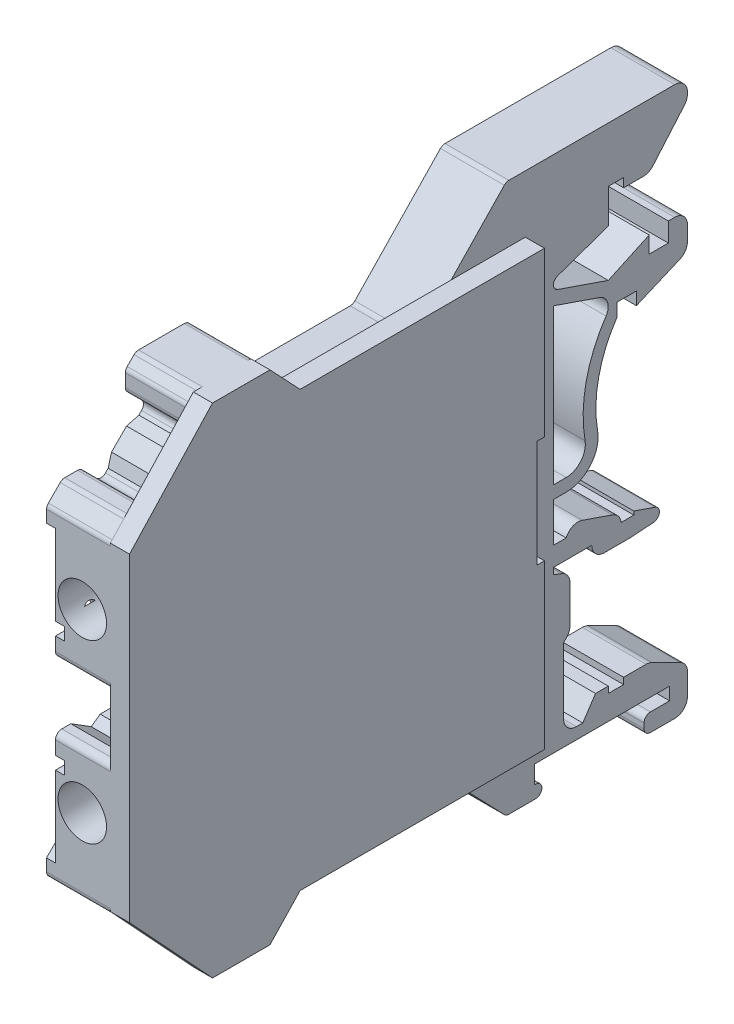
SolidWorks part; units mm, degrees
material "Polyethylene Cross-Linked"
ref_plane "Front Plane" through (0, 0, 0) normal (0, 0, 1) x (1, 0, 0)
ref_plane "Top Plane" through (0, 0, 0) normal (0, 1, 0) x (1, 0, 0)
ref_plane "Right Plane" through (0, 0, 0) normal (1, 0, 0) x (0, 0, -1)
sketch "Sketch2" plane through (0, 0, 0) normal (1, 0, 0) x (0, 0, -1)
  line L1 (-22.6, 21.5) -> (22.6, 21.5)
  line L2 (-22.6, 21.5) -> (-22.6, -21.5)
  line L3 (-22.6, -21.5) -> (22.6, -21.5)
  line L4 (22.6, 21.5) -> (22.6, -21.5)
  line L5 (-22.6, 21.5) -> (22.6, -21.5) construction
  line L6 (-22.6, -21.5) -> (22.6, 21.5) construction
  point P0 (0, 0)
  dimension "D1" = 45.2
  dimension "D2" = 43
extrude "Boss-Extrude1" add sketch "Sketch2" along normal mid plane 5
sketch "Sketch3" plane through (0, 0, 0) normal (1, 0, 0) x (0, 0, -1)
  line L0 (-22.6, 12.5) -> (-22.6, -12.5)
  line L1 (-22.6, 21.5) -> (-22.6, -21.5) construction
  line L2 (-22.6, 12.5) -> (-15.6, 19.5)
  line L3 (-15.6, 19.5) -> (-11.6, 19.5)
  line L4 (-11.6, 19.5) -> (-6.6, 14.2)
  line L5 (-6.6, 14.2) -> (1.4, 14.2)
  line L6 (1.4, 14.2) -> (8.4, 21.5)
  line L7 (-22.6, -12.5) -> (-15.6, -19.5)
  line L8 (-15.6, -19.5) -> (-11.6, -19.5)
  line L9 (8.4, 21.5) -> (15.9349, 21.5)
  line L10 (15.9349, 21.5) -> (15.9349, 44.6195)
  line L11 (15.9349, 44.6195) -> (-57.4702, 44.6195)
  line L12 (-57.4702, 44.6195) -> (-57.4702, -44.6195)
  line L13 (-57.4702, -44.6195) -> (15.9349, -44.6195)
  line L14 (15.9349, -44.6195) -> (15.9349, -21.5)
  line L15 (15.9349, -21.5) -> (8.4, -21.5)
  line L16 (8.4, -21.5) -> (1.4, -14.2)
  line L17 (1.4, -14.2) -> (-6.6, -14.2)
  line L18 (-6.6, -14.2) -> (-11.6, -19.5)
  point P5 (-22.6, 0)
  dimension "D1" = 25
  dimension "D2" = 39
  dimension "D3" = 7
  dimension "D4" = 4
  dimension "D5" = 28.4
  dimension "D6" = 16
  dimension "D7" = 8
  dimension "D8" = 43
  dimension "D9" = 31
  dimension "D10" = 7.5349
  dimension "D11" = 73.4051
  dimension "D12" = 89.239
extrude "Cut-Extrude1" cut sketch "Sketch3" against normal mid plane 25
sketch "Sketch4" plane through (2.5, 0, 0) normal (1, 0, 0) x (0, 0, -1)
  line L0 (-19.7747, 20.6036) -> (-14.8021, 15.631)
  line L1 (-19.7747, 20.6036) -> (-23.3102, 17.0681)
  line L2 (-14.8021, 15.631) -> (-18.3376, 12.0955)
  line L3 (-23.3102, 17.0681) -> (-18.3376, 12.0955)
  line L4 (-19.7747, 20.6036) -> (-18.3376, 12.0955) construction
  line L5 (-14.8021, 15.631) -> (-23.3102, 17.0681) construction
  line L6 (-22.6, 12.5) -> (-15.6, 19.5) construction
  line L8 (0, 0) -> (-48.1398, 0) construction
  line L9 (-14.8021, -15.631) -> (-23.3102, -17.0681) construction
  line L10 (-19.7747, -20.6036) -> (-18.3376, -12.0955) construction
  line L11 (-23.3102, -17.0681) -> (-18.3376, -12.0955)
  line L12 (-14.8021, -15.631) -> (-18.3376, -12.0955)
  line L13 (-19.7747, -20.6036) -> (-23.3102, -17.0681)
  line L14 (-19.7747, -20.6036) -> (-14.8021, -15.631)
  point P1 (-19.0561, 16.3495)
  point P15 (-19.0561, -16.3495)
  dimension "D1" = 5
  dimension "D2" = 3.3
  dimension "D3" = 5
  dimension "D4" = 4.9726
extrude "Cut-Extrude2" cut sketch "Sketch4" against normal mid plane 25
sketch "Sketch6" plane through (0, 0, 0) normal (1, 0, 0) x (0, 0, -1)
  line L0 (-22.6, 12.5) -> (-22.6, -12.5) construction
  line L1 (-31.6, 2.5) -> (-13.6, 2.5)
  line L2 (-31.6, 2.5) -> (-31.6, -2.5)
  line L3 (-31.6, -2.5) -> (-13.6, -2.5)
  line L4 (-13.6, 2.5) -> (-13.6, -2.5)
  line L5 (-31.6, 2.5) -> (-13.6, -2.5) construction
  line L6 (-31.6, -2.5) -> (-13.6, 2.5) construction
  point P0 (-22.6, 0)
  dimension "D1" = 5
  dimension "D2" = 18
extrude "Cut-Extrude3" cut sketch "Sketch6" against normal through all both and the other way through all
chamfer "Chamfer1" distance 1 angle 45 4 edges at (0, -17.9645, 17.1355) (0, -14.4289, 20.6711) (0, 14.4289, 20.6711) (0, 17.9645, 17.1355)
sketch "Sketch8" plane through (0, 0, 22.6) normal (0, 0, 1) x (1, 0, 0)
  line L0 (0.3, 6.9) -> (0.3, -6.9) construction
  line L1 (2.2, 6.9) -> (2.5, 6.9) construction
  line L2 (2.5, 12.5) -> (2.5, 2.5) construction
  line L3 (0, 0) -> (0.3, 0) construction
  circle A0 centre (0.3, 6.9) radius 1.9
  circle A1 centre (0.3, -6.9) radius 1.9
  point P4 (0, 0)
  dimension "D1" = 3.8
  dimension "D2" = 13.8
  dimension "D3" = 0.3
extrude "Cut-Extrude4" cut sketch "Sketch8" against normal blind 25
sketch "Sketch9" plane through (2.5, 0, 0) normal (1, 0, 0) x (0, 0, -1)
  line L0 (-15.7213, 15.4189) -> (-18.1255, 13.0147)
  line L1 (-15.7213, 15.4189) -> (-15.0142, 14.7118)
  line L2 (-18.1255, 13.0147) -> (-17.4184, 12.3076)
  line L3 (-15.0142, 14.7118) -> (-17.4184, 12.3076)
  line L4 (-15.7213, 15.4189) -> (-17.4184, 12.3076) construction
  line L5 (-18.1255, 13.0147) -> (-15.0142, 14.7118) construction
  line L6 (-18.3376, 12.0955) -> (-14.8021, 15.631) construction
  line L7 (0, 0) -> (-33.3494, 0) construction
  line L8 (-18.1255, -13.0147) -> (-15.0142, -14.7118) construction
  line L9 (-15.7213, -15.4189) -> (-17.4184, -12.3076) construction
  line L10 (-15.0142, -14.7118) -> (-17.4184, -12.3076)
  line L11 (-18.1255, -13.0147) -> (-17.4184, -12.3076)
  line L12 (-15.7213, -15.4189) -> (-15.0142, -14.7118)
  line L13 (-15.7213, -15.4189) -> (-18.1255, -13.0147)
  point P1 (-16.5698, 13.8632)
  point P14 (-16.5698, -13.8632)
  dimension "D1" = 0.5
  dimension "D2" = 3.4
extrude "Boss-Extrude2" add sketch "Sketch9" against normal up to surface (5 mm away) up to face at (-2.5, 0, 11.1692)
chamfer "Chamfer2" distance 0.5 angle 60 2 edges at (0, -13.0147, 18.1255) (0, 15.4189, 15.7213)
chamfer "Chamfer3" distance 0.5 angle 60 2 edges at (0, 13.0147, 18.1255) (0, -15.4189, 15.7213)
sketch "Sketch10" plane through (-2.5, 0, 0) normal (-1, 0, 0) x (0, 0, 1)
  line L0 (19.1, 3) -> (13.6, 3)
  line L1 (19.1, 3) -> (19.1, -3)
  line L2 (13.6, 3) -> (13.6, -3)
  line L3 (19.1, -3) -> (13.6, -3)
  line L4 (19.1, 3) -> (13.6, -3) construction
  line L5 (13.6, 3) -> (19.1, -3) construction
  line L6 (13.6, -2.5) -> (13.6, 2.5) construction
  point P0 (13.6, 0)
  point P1 (16.35, 0)
  dimension "D1" = 6
  dimension "D2" = 5.5
extrude "Cut-Extrude5" cut sketch "Sketch10" against normal blind 25
sketch "Sketch11" plane through (2.5, 0, 0) normal (1, 0, 0) x (0, 0, -1)
  line L2 (-19.8, 3.5) -> (-19.8, -3.5) construction
  line L3 (-22.6, 12.5) -> (-22.6, 2.5) construction
  line L4 (-19.1, -3) -> (-19.8, -3.5)
  line L5 (-19.8, -3.5) -> (-21.4, -2.5)
  line L6 (-22.6, -2.5) -> (-19.1, -2.5) construction
  line L7 (-21.4, -2.5) -> (-21.4, 2.5)
  line L8 (-21.4, 2.5) -> (-19.8, 3.5)
  line L9 (-19.8, 3.5) -> (-19.1, 3)
  line L10 (-19.1, 3) -> (-19.1, -3)
  line L11 (-19.1, 2.5) -> (-22.6, 2.5) construction
  circle A0 centre (-19.8, 2.9) radius 0.6 construction
  circle A1 centre (-19.8, -2.9) radius 0.6 construction
  point P6 (-19.8, 0)
  dimension "D1" = 1.2
  dimension "D4" = 1.2
  dimension "D2" = 7
  dimension "D3" = 2.8
extrude "Cut-Extrude6" cut sketch "Sketch11" against normal blind 10
sketch "Sketch12" plane through (-2.5, 0, 0) normal (-1, 0, 0) x (0, 0, 1)
  line L0 (22.6, 12.5) -> (22.6, 2.5) construction
  line L1 (33.6, 9.35) -> (11.6, 9.35)
  line L2 (33.6, 9.35) -> (33.6, -9.35)
  line L3 (33.6, -9.35) -> (11.6, -9.35)
  line L4 (11.6, 9.35) -> (11.6, -9.35)
  line L5 (33.6, 9.35) -> (11.6, -9.35) construction
  line L6 (33.6, -9.35) -> (11.6, 9.35) construction
  point P0 (22.6, 0)
  dimension "D1" = 18.7
  dimension "D2" = 11
extrude "Cut-Extrude7" cut sketch "Sketch12" against normal blind 0.7
sketch "Sketch13" plane through (-2.5, 0, 0) normal (-1, 0, 0) x (0, 0, 1)
  line L0 (22.6, 9.35) -> (22.6, 2.5) construction
  line L1 (32.2, 4.75) -> (13, 4.75)
  line L2 (32.2, 4.75) -> (32.2, 4.05)
  line L3 (32.2, 4.05) -> (13, 4.05)
  line L4 (13, 4.75) -> (13, 4.05)
  line L5 (32.2, 4.75) -> (13, 4.05) construction
  line L6 (32.2, 4.05) -> (13, 4.75) construction
  line L7 (22.6, -2.5) -> (22.6, -9.35) construction
  line L8 (32.2, -4.05) -> (13, -4.05)
  line L9 (32.2, -4.05) -> (32.2, -4.75)
  line L10 (32.2, -4.75) -> (13, -4.75)
  line L11 (13, -4.05) -> (13, -4.75)
  line L12 (32.2, -4.05) -> (13, -4.75) construction
  line L13 (32.2, -4.75) -> (13, -4.05) construction
  line L14 (0, 0) -> (27.7883, 0) construction
  line L15 (20.6, 5.75) -> (20.6, -5.75) construction
  line L16 (32.2, 4.75) -> (16.9, 4.75)
  line L17 (32.2, 4.75) -> (32.2, 5.05)
  line L18 (32.2, 5.05) -> (16.9, 5.05)
  line L19 (16.9, 4.75) -> (16.9, 5.05)
  line L20 (32.2, -4.75) -> (16.9, -4.75)
  line L21 (32.2, -4.75) -> (32.2, -5.05)
  line L22 (32.2, -5.05) -> (16.9, -5.05)
  line L23 (16.9, -4.75) -> (16.9, -5.05)
  circle A0 centre (20.6, 5.05) radius 0.7
  circle A1 centre (20.6, -5.05) radius 0.7
  point P0 (22.6, 4.4)
  point P7 (22.6, -4.4)
  dimension "D7" = 2
  dimension "D1" = 9.5
  dimension "D2" = 0.7
  dimension "D3" = 9.6
  dimension "D4" = 1
  dimension "D5" = 5.7
  dimension "D6" = 11.5
extrude "Cut-Extrude9" cut sketch "Sketch13" against normal blind 1.4 contours L2 L3 L4 L1 | L17 L18 L19 L16 | A0 | L9 L8 L11 L10 | L21 L22 L23 L20 | A1
sketch "Sketch14" plane through (0, 0, 0) normal (1, 0, 0) x (0, 0, -1)
  line L2 (-22.6, 21.5) -> (-22.6, -21.5) construction
  line L3 (16.4, 17.2) -> (17.6, 17.2)
  line L4 (16.4, 17.2) -> (16.4, -17.2)
  line L5 (16.4, -17.2) -> (17.6, -17.2)
  line L6 (17.6, 17.2) -> (17.6, -17.2)
  line L7 (16.4, 17.2) -> (17.6, -17.2) construction
  line L8 (16.4, -17.2) -> (17.6, 17.2) construction
  point P4 (17, 0)
  dimension "D1" = 34.4
  dimension "D2" = 1.2
  dimension "D3" = 39
extrude "Cut-Extrude10" cut sketch "Sketch14" against normal through all both and the other way through all
sketch "Sketch15" plane through (2.5, 0, 0) normal (1, 0, 0) x (0, 0, -1)
  line L0 (22.6, 21.5) -> (22.6, 20) construction
  line L1 (22.6, -21.5) -> (22.6, 21.5) construction
  line L2 (22.6, 20) -> (19.6, 16.5)
  line L3 (19.6, 16.5) -> (17.6, 16.5)
  line L4 (17.6, -17.2) -> (17.6, 17.2) construction
  line L5 (22.6, 21.5) -> (8.4, 21.5) construction
  line L6 (16.4, 14.5) -> (12.1, 13)
  line L7 (16.4, 17.2) -> (16.4, -17.2) construction
  line L8 (12.1, 13) -> (12.1, -7)
  line L9 (12.1, -7) -> (13.4, -7.5)
  line L10 (13.4, -7.5) -> (13.4, -11.5)
  line L11 (13.4, -11.5) -> (12.9, -12)
  line L12 (12.9, -12) -> (12.9, -16.7)
  line L13 (12.9, -16.7) -> (58.7234, -16.7)
  line L14 (-22.6, 12.5) -> (-22.6, 2.5) construction
  line L15 (22.6, 21.5) -> (8.4, 21.5) construction
  line L16 (-22.6, -2.5) -> (-22.6, -12.5) construction
  line L17 (17.6, 16.5) -> (16.4, 16.5)
  line L18 (16.4, 16.5) -> (16.4, 14.5)
  line L19 (22.6, 20) -> (58.7234, 20)
  line L20 (58.7234, 20) -> (58.7234, -16.7)
  dimension "D1" = 5
  dimension "D2" = 1.5
  dimension "D3" = 2
  dimension "D4" = 34.7
  dimension "D5" = 8.5
  dimension "D6" = 7
  dimension "D7" = 20
  dimension "D8" = 5
  dimension "D9" = 4.7
  dimension "D10" = 36
  dimension "D11" = 0.5
  dimension "D12" = 0.5
  dimension "D13" = 4
  dimension "D14" = 35.5
  dimension "D15" = 36.1234
extrude "Cut-Extrude11" cut sketch "Sketch15" against normal blind 7
sketch "Sketch16" plane through (2.5, 0, 0) normal (1, 0, 0) x (0, 0, -1)
  line L0 (12.1, 12.3) -> (16.4, 10.8194)
  line L1 (12.1, 13) -> (12.1, -7) construction
  line L2 (16.4, 10.8194) -> (19.6, 12.3)
  line L3 (19.6, 12.3) -> (19.6, 11)
  line L4 (19.6, 11) -> (21.1, 11)
  line L5 (21.1, 11) -> (21.1, 12.5)
  line L6 (21.1, 12.5) -> (22.6, 12.5)
  line L7 (22.6, 12.5) -> (22.6, 9.7)
  line L8 (22.6, 9.7) -> (18.6, 8)
  line L9 (18.6, 8) -> (18.6, 9)
  line L10 (18.6, 9) -> (17.1, 9)
  line L11 (17.1, 9) -> (17.1, 8)
  line L12 (22.6, 21.5) -> (22.6, -21.5) construction
  line L13 (-22.6, 21.5) -> (22.6, 21.5) construction
  line L14 (12.1, -1.9) -> (14.7278, -1.9) construction
  line L15 (13.1, -1.9) -> (12.1, -1.9)
  line L16 (12.1, -1.9) -> (12.1, 12.3)
  arc A0 (17.1, 8) -> (15.5644, 1.0206) centre (24.929, 2.6188) ccw
  arc A1 (15.5644, 1.0206) -> (13.1, -1.9) centre (13.1, 0.6) cw
  dimension "D13" = 2.5
  dimension "D15" = 9.5
  dimension "D1" = 109
  dimension "D2" = 0.7
  dimension "D3" = 1.5
  dimension "D4" = 1.5
  dimension "D5" = 9
  dimension "D6" = 1.5
  dimension "D7" = 4.5
  dimension "D8" = 2.8
  dimension "D9" = 4
  dimension "D10" = 1.5
  dimension "D11" = 1
  dimension "D12" = 23.4
  dimension "D14" = 1
extrude "Boss-Extrude3" add sketch "Sketch16" against normal up to surface (5 mm away) up to face at (-2.5, -0.4418, 3.4082)
sketch "Sketch17" plane through (2.5, 0, 0) normal (1, 0, 0) x (0, 0, -1)
  line L2 (12.1, -0.9) -> (13.1, -0.9)
  line L3 (12.1, -0.9) -> (13.1, -0.9)
  line L4 (12.1, 12.3) -> (12.1, -1.9) construction
  line L5 (16.0744, 9.8739) -> (11.7744, 11.3545)
  line L6 (15.721, 9.9956) -> (12.1, 11.2424)
  line L7 (12.1, 11.2424) -> (12.1, -0.9)
  arc A5 (16.2244, 8.4908) -> (15.721, 9.9956) centre (15.3954, 9.0501) ccw
  arc A7 (16.2759, 8.5664) -> (14.5786, 0.8524) centre (24.929, 2.6188) ccw
  arc A8 (13.1, -0.9) -> (14.5786, 0.8524) centre (13.1, 0.6) ccw
  arc A9 (16.2244, 8.4908) -> (14.5786, 0.8524) centre (24.929, 2.6188) ccw
  arc A10 (13.1, -0.9) -> (14.5786, 0.8524) centre (13.1, 0.6) ccw
  dimension "D3" = 1
  dimension "D1" = 1
  dimension "D2" = 1
extrude "Cut-Extrude12" cut sketch "Sketch17" against normal blind 7
sketch "Sketch18" plane through (2.5, 0, 0) normal (1, 0, 0) x (0, 0, -1)
  line L0 (12.1, -5) -> (13.1, -5)
  line L1 (12.1, -1.9) -> (12.1, -7) construction
  line L2 (13.1, -5) -> (13.1, -4)
  line L3 (13.1, -4) -> (17.4, -5.4806)
  line L4 (17.4, -5.4806) -> (17.4, -6.1)
  line L5 (17.4, -6.1) -> (18.4, -6.1)
  line L6 (18.4, -6.1) -> (18.4, -5.8249)
  line L7 (18.4, -5.8249) -> (20.067, -6.3989)
  line L8 (19.9394, -7.3705) -> (18.1, -7.5)
  line L9 (18.1, -7.5) -> (15.1, -7.5)
  line L10 (15.1, -7.5) -> (15.1, -6.5)
  line L11 (15.1, -6.5) -> (12.1, -6.5)
  line L12 (12.1, -6.5) -> (12.1, -5)
  line L13 (16.4, 10.8194) -> (12.1, 12.3) construction
  line L14 (-22.6, -2.5) -> (-22.6, -12.5) construction
  line L15 (20.4, -6.9368) -> (20.4, -8.2286) construction
  line L16 (-22.6, 21.5) -> (22.6, 21.5) construction
  line L17 (-22.6, 21.5) -> (-22.6, -21.5) construction
  arc A0 (20.067, -6.3989) -> (19.9394, -7.3705) centre (19.9043, -6.8717) cw
  dimension "D10" = 0.5
  dimension "D1" = 1.5
  dimension "D2" = 3.5
  dimension "D3" = 1.4
  dimension "D4" = 1
  dimension "D5" = 1
  dimension "D6" = 1
  dimension "D7" = 40
  dimension "D8" = 3
  dimension "D9" = 3
  dimension "D11" = 29
  dimension "D12" = 43
extrude "Boss-Extrude4" add sketch "Sketch18" against normal up to surface (5 mm away) up to face at (-2.5, 4.7868, -13.9775)
sketch "Sketch20" plane through (2.5, 0, 0) normal (1, 0, 0) x (0, 0, -1)
  line L0 (12.9, -16.7) -> (12.9, -18.2)
  line L1 (12.9, -18.2) -> (14.4, -18.2)
  line L2 (14.4, -18.2) -> (15.4, -16.7)
  line L3 (12.9, -16.7) -> (16.4, -16.7) construction
  line L4 (15.4, -16.7) -> (12.9, -16.7)
  line L5 (19.6, -16.7) -> (22.6, -18.2)
  line L6 (17.6, -16.7) -> (22.6, -16.7) construction
  line L7 (22.6, 21.5) -> (22.6, -21.5) construction
  line L8 (22.6, -18.2) -> (22.6, -16.7)
  line L9 (22.6, -16.7) -> (19.6, -16.7)
  line L10 (-22.6, -21.5) -> (22.6, -21.5) construction
  line L11 (21.2, -20.1) -> (11.2, -20.1)
  line L12 (21.2, -20.1) -> (21.2, -19.1)
  line L13 (21.2, -19.1) -> (11.2, -19.1)
  line L14 (11.2, -20.1) -> (11.2, -19.1)
  line L15 (21.2, -20.1) -> (11.2, -19.1) construction
  line L16 (21.2, -19.1) -> (11.2, -20.1) construction
  line L18 (19.2, -20.1) -> (11.2, -20.1)
  line L19 (19.2, -20.1) -> (19.2, -24.6238)
  line L20 (19.2, -24.6238) -> (11.2, -24.6238)
  line L21 (11.2, -20.1) -> (11.2, -24.6238)
  point P15 (16.2, -19.6)
  dimension "D1" = 1.5
  dimension "D2" = 2.5
  dimension "D3" = 1.5
  dimension "D4" = 3
  dimension "D5" = 1.5
  dimension "D6" = 1
  dimension "D7" = 10
  dimension "D8" = 1.4
  dimension "D9" = 1.4
  dimension "D10" = 3.4
  dimension "D11" = 8
  dimension "D12" = 4.5238
extrude "Cut-Extrude13" cut sketch "Sketch20" against normal blind 7 contours L2 L4 L0 L1 | L8 L9 L5 | L11 L21 L20 L19 | L14 L11 L12 L13
fillet "Fillet1" radius 1 14 edges at (0, 12.5, -22.6) (0, 9.7, -22.6) (0, 16.5, -19.6) (0, 20, -22.6) (0, 21.5, -22.6) (0, -7.5, -15.1) (0, -4, -13.1) (0, -5.4806, -17.4) (0, -7.5, -13.4) (0, -11.5, -13.4) (0, -18.2, -12.9) (0, -21.5, -22.6) (0, -18.2, -22.6) (0, -16.7, -19.6)
sketch "Sketch21" plane through (-2.5, 0, 0) normal (-1, 0, 0) x (0, 0, 1)
  line L1 (-12.1, 20.2) -> (-17.1, 20.2)
  line L2 (-12.1, 20.2) -> (-12.1, 18.2)
  line L3 (-12.1, 18.2) -> (-17.1, 18.2)
  line L4 (-17.1, 20.2) -> (-17.1, 18.2)
  line L5 (-12.1, 20.2) -> (-17.1, 18.2) construction
  line L6 (-12.1, 18.2) -> (-17.1, 20.2) construction
  line L9 (-12.1, 14.0591) -> (-12.1, 18.2)
  line L10 (-12.1, 13) -> (-12.1, 12.3) construction
  line L11 (-15.4, 15.2103) -> (-11.7706, 13.9442)
  line L12 (-15.4, 17.2) -> (-15.4, 15.2103)
  line L13 (-15.4, 15.2103) -> (-12.1, 14.0591)
  line L14 (-15.4, 18.2) -> (-15.4, 15.2103)
  line L15 (-17.6, 17.2) -> (-16.4, 17.2) construction
  point P0 (-14.6, 19.2)
  dimension "D2" = 2
  dimension "D3" = 1
  dimension "D4" = 5
  dimension "D1" = 1
extrude "Cut-Extrude14" cut sketch "Sketch21" against normal blind 2 contours L1 L4 L3 L2 | L3 L14 L13 L9
sketch "Sketch22" plane through (-2.5, 0, 0) normal (-1, 0, 0) x (0, 0, 1)
  line L2 (-2.1218, 13.5079) -> (-9.1218, 20.8079)
  line L3 (-3.6, 15.0494) -> (-8.8266, 20.5)
  line L5 (-9.1218, -20.8079) -> (-2.1218, -13.5079)
  line L6 (-8.8266, -20.5) -> (-3.6, -15.0494)
  line L8 (-11.1, 11.2424) -> (-11.1, -0.9)
  line L9 (-11.1, 20.5) -> (-11.1, -20.5)
  line L11 (-21.6, 20.5) -> (-8.4, 20.5)
  line L12 (-11.1, 20.5) -> (-8.8266, 20.5)
  line L13 (-3.6, 15.0494) -> (-3.6, -15.0494)
  line L14 (-8.4, -20.5) -> (-11.2, -20.5)
  line L15 (-8.8266, -20.5) -> (-11.1, -20.5)
  dimension "D6" = 7.5
  dimension "D1" = 1
  dimension "D2" = 1
  dimension "D3" = 1
  dimension "D4" = 1
  dimension "D5" = 1
extrude "Cut-Extrude15" cut sketch "Sketch22" against normal blind 1.5
chamfer "Chamfer4" distance 2 angle 30 1 edges at (-1, 0, -3.6)
sketch "Sketch23" plane through (-1, 0, 0) normal (-1, 0, 0) x (0, 0, 1)
  line L0 (-11.1, 20.5) -> (-11.1, -20.5) construction
  line L1 (11.1, 1.5) -> (-11.1, 1.5)
  line L2 (11.1, 1.5) -> (11.1, -1.5)
  line L3 (11.1, -1.5) -> (-11.1, -1.5)
  line L4 (-11.1, 1.5) -> (-11.1, -1.5)
  line L5 (11.1, 1.5) -> (-11.1, -1.5) construction
  line L6 (11.1, -1.5) -> (-11.1, 1.5) construction
  point P0 (0, 0)
  dimension "D1" = 3
extrude "Boss-Extrude5" add sketch "Sketch23" along normal blind 1
sketch "Sketch24" plane through (-2.5, 0, 0) normal (-1, 0, 0) x (0, 0, 1)
  line L0 (-3.6, 15.0494) -> (-3.6, -15.0494) construction
  line L1 (-2.6, 12.25) -> (-4.6, 12.25)
  line L2 (-2.6, 12.25) -> (-2.6, 8.75)
  line L3 (-2.6, 8.75) -> (-4.6, 8.75)
  line L4 (-4.6, 12.25) -> (-4.6, 8.75)
  line L5 (-2.6, 12.25) -> (-4.6, 8.75) construction
  line L6 (-2.6, 8.75) -> (-4.6, 12.25) construction
  line L7 (-3.6, -15.0494) -> (-3.6, 15.0494) construction
  line L8 (-2.6, -8.75) -> (-4.6, -8.75)
  line L9 (-2.6, -8.75) -> (-2.6, -12.25)
  line L10 (-2.6, -12.25) -> (-4.6, -12.25)
  line L11 (-4.6, -8.75) -> (-4.6, -12.25)
  line L12 (-2.6, -8.75) -> (-4.6, -12.25) construction
  line L13 (-2.6, -12.25) -> (-4.6, -8.75) construction
  line L14 (0, 0) -> (-21.9905, 0) construction
  line L15 (-11.1, 20.5) -> (-11.1, -20.5) construction
  point P0 (-3.6, 10.5)
  point P7 (-3.6, -10.5)
  dimension "D1" = 3.5
  dimension "D2" = 24.5
  dimension "D3" = 6.5
extrude "Boss-Extrude6" add sketch "Sketch24" against normal blind 3
chamfer "Chamfer5" distance 2 angle 45 4 edges at (-2.15, -9.35, 22.6) (-2.15, 9.35, 22.6) (-2.15, -9.35, 11.6) (-2.15, 9.35, 11.6)
sketch "Sketch25" plane through (-1, 0, 0) normal (-1, 0, 0) x (0, 0, 1)
  line L0 (-11.1, -20.5) -> (-8.8266, -20.5) construction
  line L1 (-11.2, -19.1) -> (-10.6098, -19.1)
  line L2 (-11.2, -19.1) -> (-11.2, -20.5)
  line L3 (-11.2, -20.5) -> (-10.6098, -20.5)
  line L4 (-10.6098, -19.1) -> (-10.6098, -20.5)
extrude "Cut-Extrude16" cut sketch "Sketch25" against normal through all both and the other way through all
fillet "Fillet2" radius 0.5 31 edges at (0, -15.631, 14.8021) (0, -12.0955, 18.3376) (0, 12.0955, 18.3376) (0.35, -2.5, 22.6) (0.35, 2.5, 22.6) (0, -17.2574, 16.4284) (0, -19.5, 11.6) (0, -19.5, 15.6) (0, -18.6716, 16.4284) (0, -13.7218, 19.964) (0, -12.5, 22.6) (0, -13.7218, 21.3782) (0, 17.2574, 16.4284) (0, 15.631, 14.8021) (0, 12.5, 22.6) (0, 13.7218, 21.3782) (0, 13.7218, 19.964) (0, 18.6716, 16.4284) (0, 19.5, 15.6) (0, 19.5, 11.6) (0, 14.2, 6.6) (0, 21.5, -8.4) (0, 14.2, -1.4) (0, -14.2, -1.4) (0, -21.5, -8.4) (0, -21.5, -11.2) (0, -20.5, -11.2) (0, -20.1, -19.2) (0, -21.5, -19.2) (0, 13, -12.1) (0, 12.3, -12.1)
sketch "Sketch26" plane through (2.5, 0, 0) normal (1, 0, 0) x (0, 0, -1)
  line L0 (-22.6, 12.5) -> (-22.6, -12.5)
  line L1 (-22.6, -12.5) -> (-16.1, -19.5)
  line L2 (-16.1, -19.5) -> (-11.6, -19.5)
  line L3 (-11.6, -19.5) -> (-9.2415, -17)
  line L4 (-9.2415, -17) -> (9.9, -17)
  line L5 (9.9, -17) -> (9.9, 17)
  line L6 (9.9, 17) -> (-9.2415, 17)
  line L7 (-9.2415, 17) -> (-11.6, 19.5)
  line L8 (-11.6, 19.5) -> (-16.1, 19.5)
  line L9 (-16.1, 19.5) -> (-22.6, 12.5)
  line L10 (-22.6, -3) -> (-22.6, -12.2929) construction
  line L11 (-11.452, 19.3431) -> (-6.748, 14.3569) construction
  line L12 (-6.6, -14.2) -> (-11.452, -19.3431) construction
  line L14 (10.5, 4.2) -> (9.3, 4.2)
  line L15 (10.5, 4.2) -> (10.5, -4.2)
  line L16 (10.5, -4.2) -> (9.3, -4.2)
  line L17 (9.3, 4.2) -> (9.3, -4.2)
  line L18 (10.5, 4.2) -> (9.3, -4.2) construction
  line L19 (10.5, -4.2) -> (9.3, 4.2) construction
  point P3 (-22.6, 0)
  point P18 (9.9, 0)
  dimension "D1" = 25
  dimension "D2" = 39
  dimension "D3" = 34
  dimension "D4" = 32.5
  dimension "D5" = 8.4
  dimension "D6" = 4.5
  dimension "D7" = 1.2
extrude "Boss-Extrude7" add sketch "Sketch26" along normal blind 1.5 contours L17 L14 L5 L6 L7 L8 L9 L0 L1 L2 L3 L4 L16
